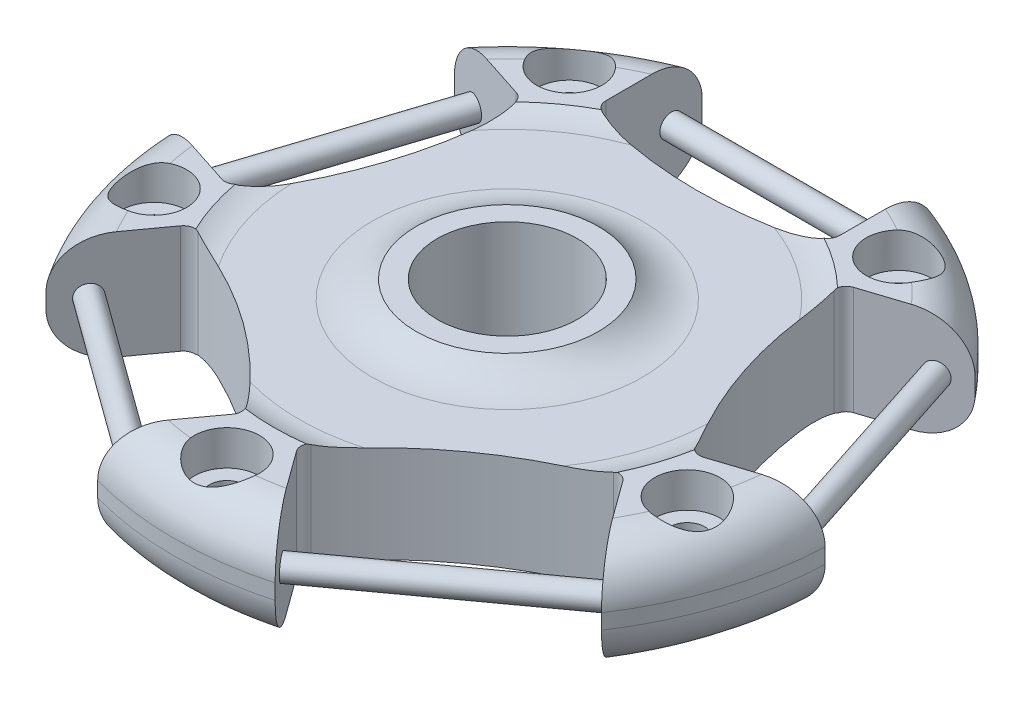
SolidWorks part; units mm, degrees
other "Camera1"
ref_plane "Front Plane" through (0, 0, 0) normal (0, 0, 1) x (1, 0, 0)
ref_plane "Top Plane" through (0, 0, 0) normal (0, 1, 0) x (1, 0, 0)
ref_plane "Right Plane" through (0, 0, 0) normal (1, 0, 0) x (0, 0, -1)
sketch "Sketch1" plane through (0, 0, 0) normal (0, 1, 0) x (1, 0, 0)
  line L0 (0, 0) -> (0, 50000) construction
  line L1 (0, 0) -> (-50000, 0) construction
  circle A0 centre (0, 0) radius 28.5
  dimension "D1" = 57
extrude "Boss-Extrude1" add sketch "Sketch1" along normal blind 9.3
fillet "Fillet13" radius 4 2 edges at (0, 9.3, 28.5) (0, 0, 28.5)
sketch "Sketch2" plane through (0, 9.3, 0) normal (0, 1, 0) x (1, 0, 0)
  line L0 (0, 0) -> (13.4182, 0) construction
  line L1 (0, 0) -> (0, 50000) construction
  line L2 (10, 26.688) -> (10, 17.688)
  line L3 (-10, 26.688) -> (-10, 17.688)
  circle A0 centre (0, 0) radius 28.5 construction
  arc A1 (-10, 17.688) -> (10, 17.688) centre (0, 50.0973) ccw
  arc A2 (-10, 26.688) -> (10, 26.688) centre (0, 0) cw
  dimension "D1" = 9
  dimension "D2" = 10
extrude "Cut-Extrude1" cut sketch "Sketch2" against normal through all
pattern_circular "CirPattern1" count 5 over 360 about axis through (0, 0, 0) along (0, -1, 0) of "Cut-Extrude1"
sketch "Sketch3" plane through (0, 9.3, 0) normal (0, 1, 0) x (1, 0, 0)
  circle A0 centre (0, 0) radius 6
  circle A1 centre (0, 0) radius 7.8
  dimension "D1" = 1.8
  dimension "D2" = 12
extrude "Cut-Extrude2" cut sketch "Sketch3" against normal through all contours A0 region at (0, 9.3, 0)
ref_plane "Plane1" through (0, 4.65, 0) normal (0, 1, 0) x (1, 0, 0)
sketch "Sketch8" plane through (0, 4.65, 0) normal (0, 1, 0) x (1, 0, 0)
  circle A0 centre (0, 0) radius 20
  dimension "D1" = 40
extrude "Cut-Extrude5" cut sketch "Sketch8" against normal blind 0.5 from surface starting at face at (0, 9.3, 6)
sketch "Sketch5" plane through (0, 9.3, 0) normal (0, 1, 0) x (1, 0, 0)
  line L0 (0, 0) -> (0, -50000) construction
  circle A0 centre (0, -24) radius 2.8
  circle A1 centre (0, -24) radius 1.5
  dimension "D1" = 24
  dimension "D2" = 5.6
extrude "Cut-Extrude4" cut sketch "Sketch5" against normal through all contours L0 A1 | A1 L0 region at (0.6366, 9.3, 24) region at (-0.6366, 9.3, 24)
pattern_circular "CirPattern2" count 5 over 360 about axis through (0, 8.8, 0) along (0, -1, 0) of "Cut-Extrude4"
sketch "Sketch7" plane through (-8.0902, 0, 5.8779) normal (0.809, 0, -0.5878) x (-0.5878, 0, -0.809)
  line L1 (-33.8543, 4.65) -> (-18.0591, 4.65) construction
  line L5 (-20.0271, 10) -> (-20.0271, 0) construction
  line L7 (-17.688, 0) -> (-22.3663, 0) construction
  circle A0 centre (-24.0591, 4.65) radius 1
  point P0 (-25.9567, 4.65)
  point P1 (-20.0271, 5)
  dimension "D1" = 2
  dimension "D2" = 6
extrude "Boss-Extrude2" add sketch "Sketch7" along normal up to next
pattern_circular "CirPattern3" count 5 over 360 about axis through (0, 8.8, 0) along (0, -1, 0) of "Boss-Extrude2"
extrude "Boss-Extrude3" add sketch "Sketch3<2>" along normal blind 1 and the other way blind 6
sketch "Sketch3<2>" plane through (0, 9.3, 0) normal (0, 1, 0) x (1, 0, 0) same geometry as "Sketch3"
extrude "Cut-Extrude7" cut sketch "Sketch8<2>" along normal blind 0.5 from surface starting at face at (0, 0, 6)
sketch "Sketch8<2>" plane through (0, 4.65, 0) normal (0, 1, 0) x (1, 0, 0) same geometry as "Sketch8"
extrude "Boss-Extrude4" add sketch "Sketch3<4>" against normal blind 1 from surface starting at face at (0, 0.5, 0)
sketch "Sketch3<4>" plane through (0, 9.3, 0) normal (0, 1, 0) x (1, 0, 0) same geometry as "Sketch3"
fillet "Fillet3" radius 5.5 2 edges at (0, 8.8, 7.8) (0, 0.5, 7.8)
fillet "Fillet4" radius 5 10 edges at (0, 0.5, 20) (19.0211, 0.5, 6.1803) (11.7557, 0.5, -16.1803) (-11.7557, 0.5, -16.1803) (-19.0211, 0.5, 6.1803) (19.0211, 8.8, 6.1803) (11.7557, 8.8, -16.1803) (0, 8.8, 20) (-19.0211, 8.8, 6.1803) (-11.7557, 8.8, -16.1803)
fillet "Fillet14" radius 1 10 edges at (18.4869, 4.65, 8.4321) (19.9125, 4.65, 4.0447) (13.7321, 4.65, -14.9765) (10, 4.65, -17.688) (-10, 4.65, -17.688) (-13.7321, 4.65, -14.9765) (-19.9125, 4.65, 4.0447) (-18.4869, 4.65, 8.4321) (-2.3066, 4.65, 20.1878) (2.3066, 4.65, 20.1878)
extrude "Cut-Extrude8" cut sketch "Sketch5<3>" against normal blind 3 contours L0 A0 A1 | A0 L0 A1 region at (1.9356, 9.3, 22.0644) region at (-0.0626, 9.3, 21.85)
sketch "Sketch5<3>" plane through (0, 9.3, 0) normal (0, 1, 0) x (1, 0, 0) same geometry as "Sketch5"
pattern_circular "CirPattern4" count 5 over 360 about axis through (0, 10.3, 0) along (0, 1, 0) of "Cut-Extrude8"
sketch "Sketch9" plane through (0, 0, 0) normal (0, 1, 0) x (1, 0, 0)
  line L1 (16.9166, 20.8958) -> (14.2305, 22.5894)
  line L2 (14.2305, 22.5894) -> (11.4208, 21.11)
  line L3 (11.4208, 21.11) -> (11.2971, 17.937)
  line L4 (11.2971, 17.937) -> (13.9832, 16.2434)
  line L5 (13.9832, 16.2434) -> (16.7929, 17.7228)
  line L6 (16.7929, 17.7228) -> (16.9166, 20.8958)
  circle A0 centre (14.1068, 19.4164) radius 2.75 construction
  dimension "D1" = 5.5
extrude "Cut-Extrude9" cut sketch "Sketch9" along normal blind 3
pattern_circular "CirPattern5" count 5 over 360 about axis through (0, -0.5, 0) along (0, 1, 0) of "Cut-Extrude9"
